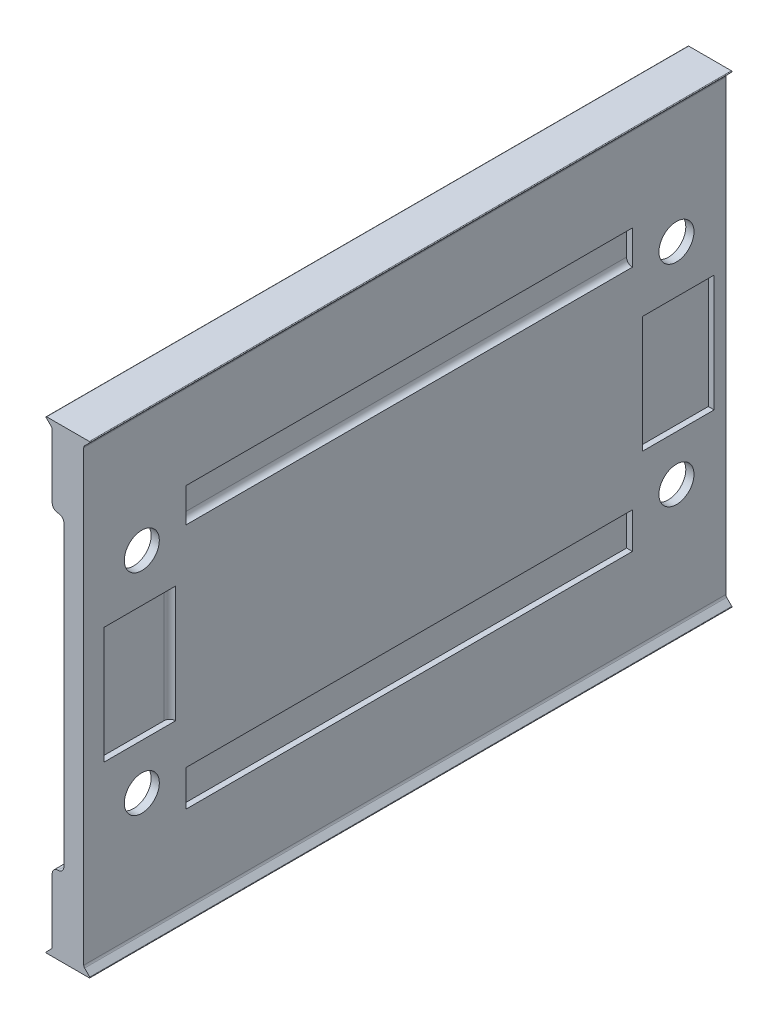
SolidWorks part; units mm, degrees
ref_plane "Front Plane" through (0, 0, 0) normal (0, 0, 1) x (1, 0, 0)
ref_plane "Top Plane" through (0, 0, 0) normal (0, 1, 0) x (1, 0, 0)
ref_plane "Right Plane" through (0, 0, 0) normal (1, 0, 0) x (0, 0, -1)
sketch "Sketch1" plane through (0, 0, 0) normal (0, 0, 1) x (1, 0, 0)
  line L0 (-1.8293, 19.9) -> (1.8293, 19.9)
  line L1 (0, 22.5) -> (0, -22.5) construction
  line L2 (-1.8646, 19.8146) -> (-1.4232, 19.3732)
  line L7 (1.8646, 19.8146) -> (1.4232, 19.3732)
  line L8 (-20, 0) -> (20, 0) construction
  line L11 (-1.8646, -19.8146) -> (-1.4232, -19.3732)
  line L12 (-1.8293, -19.9) -> (1.8293, -19.9)
  line L13 (1.8646, -19.8146) -> (1.4232, -19.3732)
  line L16 (-1.35, 19.1929) -> (-1.35, -19.2)
  line L17 (1.35, 19.1964) -> (1.35, -19.1964)
  arc A3 (-1.4232, 19.3732) -> (-1.35, 19.1929) centre (-1.6, 19.1964) cw
  arc A7 (1.4232, 19.3732) -> (1.35, 19.1964) centre (1.6, 19.1964) ccw
  arc A8 (1.8293, 19.9) -> (1.8646, 19.8146) centre (1.8293, 19.85) cw
  arc A9 (-1.8293, 19.9) -> (-1.8646, 19.8146) centre (-1.8293, 19.85) ccw
  arc A12 (-1.4232, -19.3732) -> (-1.35, -19.2) centre (-1.6, -19.1964) ccw
  arc A13 (-1.8293, -19.9) -> (-1.8646, -19.8146) centre (-1.8293, -19.85) cw
  arc A14 (1.8293, -19.9) -> (1.8646, -19.8146) centre (1.8293, -19.85) ccw
  arc A15 (1.4232, -19.3732) -> (1.35, -19.1964) centre (1.6, -19.1964) cw
  point P0 (1.35, 0)
  point P1 (0, 0)
  point P8 (0, 19.9)
  point P30 (1.95, 19.9)
  point P33 (-1.95, 19.9)
  dimension "D1" = 39.8
  dimension "D2" = 2.7
  dimension "D7" = 0.7071
  dimension "D8" = 0.25
  dimension "D9" = 0.05
  dimension "D3" = 3.9
  dimension "D4" = 45
extrude "Boss-Extrude1" add sketch "Sketch1" along normal blind 55
sketch "Sketch2" plane through (1.35, 0, 0) normal (1, 0, 0) x (0, 0, -1)
  line L0 (-71.3614, -146.3971) -> (297.3053, -146.3971) construction
  line L5 (-50.025, 9.0879) -> (-50.025, -8.9121) construction
  line L6 (-51.25, 12) -> (-3, 12)
  line L7 (-53.25, 10) -> (-53.25, -10)
  line L8 (-51.25, -12) -> (-3, -12)
  line L9 (-1, 10) -> (-1, -10)
  line L10 (-50.025, 9.0879) -> (-4.225, 9.0879) construction
  line L11 (-55, -19.1964) -> (-55, 19.1964) construction
  line L12 (-4.225, -8.9121) -> (-50.025, -8.9121) construction
  line L13 (-4.225, 9.0879) -> (-4.225, -8.9121) construction
  line L14 (-27.125, 9.0879) -> (-27.125, -8.9121) construction
  line L15 (-47.125, 9.0879) -> (-7.125, 9.0879)
  line L16 (-47.125, 9.0879) -> (-47.125, -8.9121)
  line L17 (-47.125, -8.9121) -> (-7.125, -8.9121)
  line L18 (-7.125, 9.0879) -> (-7.125, -8.9121)
  line L19 (-53.25, 0) -> (-31.25, 0) construction
  arc A0 (-53.25, 10) -> (-51.25, 12) centre (-51.25, 10) cw
  arc A1 (-3, 12) -> (-1, 10) centre (-3, 10) cw
  arc A2 (-1, -10) -> (-3, -12) centre (-3, -10) cw
  circle A3 centre (-50.025, 9.0879) radius 2.5
  circle A4 centre (-50.025, -8.9121) radius 2.5
  circle A5 centre (-4.225, -8.9121) radius 2.5
  circle A6 centre (-4.225, 9.0879) radius 2.5
  arc A7 (-51.25, -12) -> (-53.25, -10) centre (-51.25, -10) cw
  point P12 (-1, -12)
  point P23 (-55, 0)
  point P24 (-27.125, -8.9121)
  point P31 (-27.125, 12)
  point P34 (-53.25, -12)
  dimension "D1" = 24
  dimension "D3" = 2
  dimension "D10" = 5
  dimension "D11" = 5
  dimension "D12" = 5
  dimension "D13" = 5
  dimension "D18" = 2
  dimension "D2" = 52.25
  dimension "D4" = 18
  dimension "D5" = 45.8
  dimension "D6" = 2.9121
  dimension "D8" = 1.75
  dimension "D14" = 18
  dimension "D15" = 45.8
  dimension "D16" = 40
  dimension "D17" = 18
sketch "Sketch4" plane through (-1.35, 0, 0) normal (-1, 0, 0) x (0, 0, 1)
  line L0 (116.9009, 229.5811) -> (508.9009, 229.5811) construction
  line L5 (-215.0482, -19.301) -> (-235.2775, 269.9925) construction
extrude "Cut-Extrude4" cut sketch "Sketch2" against normal blind 0.5
sketch "Sketch7" plane through (1.35, 0, 0) normal (1, 0, 0) x (0, 0, -1)
  circle A0 centre (-50.025, 9.0879) radius 1.5
  circle A1 centre (-4.225, 9.0879) radius 1.5
  circle A2 centre (-4.225, -8.9121) radius 1.5
  circle A3 centre (-50.025, -8.9121) radius 1.5
  dimension "D1" = 3
  dimension "D2" = 3
  dimension "D3" = 3
  dimension "D4" = 3
extrude "Cut-Extrude7" cut sketch "Sketch7" against normal through all
sketch "Sketch8" plane through (-1.35, 0, 0) normal (-1, 0, 0) x (0, 0, 1)
  circle A0 centre (4.225, 9.0879) radius 3.75
  circle A1 centre (4.225, -8.9121) radius 3.75
  circle A2 centre (50.025, 9.0879) radius 3.75
  circle A3 centre (50.025, -8.9121) radius 3.75
  dimension "D1" = 7.5
  dimension "D2" = 7.5
  dimension "D3" = 7.5
  dimension "D4" = 7.5
extrude "Cut-Extrude8" cut sketch "Sketch8" against normal blind 2
sketch "Sketch9" plane through (-1.35, 0, 0) normal (-1, 0, 0) x (0, 0, 1)
  line L0 (0, 0) -> (55, 0) construction
  line L2 (0, 19.1929) -> (0, -19.2) construction
  line L3 (55, 13.25) -> (0, 13.25)
  line L4 (55, 13.25) -> (55, -13.25)
  line L5 (55, -13.25) -> (0, -13.25)
  line L6 (0, 13.25) -> (0, -13.25)
  line L7 (55, 13.25) -> (0, -13.25) construction
  line L8 (55, -13.25) -> (0, 13.25) construction
  line L9 (55, 19.1929) -> (55, -19.2) construction
  point P5 (27.5, 0)
  dimension "D1" = 26.5
extrude "Cut-Extrude9" cut sketch "Sketch9" against normal blind 1
fillet "Fillet1" radius 0.5 2 edges at (-0.35, -13.25, 27.5) (-0.35, 13.25, 27.5)
fillet "Fillet2" radius 0.5 2 edges at (-1.35, -13.25, 27.5) (-1.35, 13.25, 27.5)
fillet "Fillet4" radius 0.5 4 edges at (0.85, 0.0879, 7.125) (0.85, -8.9121, 27.125) (0.85, 9.0879, 27.125) (0.85, 0.0879, 47.125)
fillet "Fillet5" radius 0.5 4 edges at (0.65, 5.3379, 4.225) (0.65, -12.6621, 4.225) (0.65, -12.6621, 50.025) (0.65, 5.3379, 50.025)
sketch "Sketch10" plane through (0.85, 0, 0) normal (1, 0, 0) x (0, 0, -1)
  line L1 (-53.25, 10) -> (-53.25, -10) construction
  line L2 (-3, 12) -> (-51.25, 12) construction
  line L3 (-8, 12) -> (-1, 12)
  line L4 (-1, 12) -> (-1, 5)
  line L5 (-1, -10) -> (-1, 10) construction
  line L6 (-1, 5) -> (-8, 5)
  line L8 (-3, 12) -> (-51.25, 12) construction
  line L11 (-8, 12) -> (-8, 5)
  line L12 (-46.25, -12) -> (-46.25, -5)
  line L13 (-1, -12) -> (-8, -12)
  line L14 (-1, -12) -> (-1, -5)
  line L15 (-1, -5) -> (-8, -5)
  line L16 (-8, -12) -> (-8, -5)
  line L17 (-53.25, -5) -> (-46.25, -5)
  line L18 (-51.25, -12) -> (-3, -12) construction
  line L19 (-53.25, -12) -> (-53.25, -5)
  line L21 (-53.25, -12) -> (-46.25, -12)
  line L22 (-46.25, 12) -> (-46.25, 5)
  line L23 (-53.25, 5) -> (-46.25, 5)
  line L24 (-53.25, 12) -> (-53.25, 5)
  line L25 (-46.25, 12) -> (-53.25, 12)
  circle A0 centre (-4.225, 9.0879) radius 1.5
  circle A1 centre (-4.225, -8.9121) radius 1.5
  circle A2 centre (-4.225, -8.9121) radius 1.5 construction
  circle A3 centre (-50.025, -8.9121) radius 1.5
  circle A4 centre (-50.025, 9.0879) radius 1.5
  circle A5 centre (-50.025, -8.9121) radius 1.5 construction
  circle A6 centre (-50.025, 9.0879) radius 1.5 construction
  point P25 (0, 0)
  point P42 (-46.25, 5)
  dimension "D3" = 3
  dimension "D1" = 7
  dimension "D2" = 7
  dimension "D4" = 7
  dimension "D5" = 7
  dimension "D6" = 7
  dimension "D7" = 7
  dimension "D8" = 7
  dimension "D9" = 7
extrude "Boss-Extrude3" add sketch "Sketch10" along normal up to surface (0.5 mm away) up to face at (1.35, 0.0879, 27.125)
